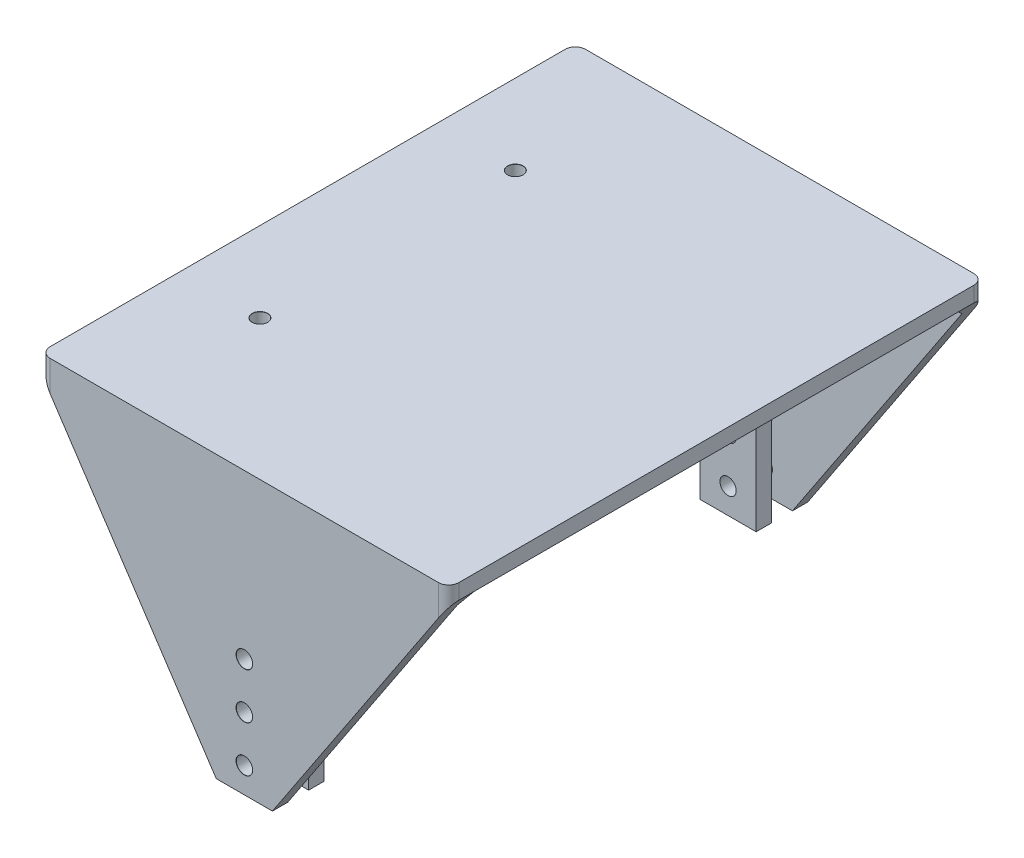
SolidWorks part; units mm, degrees
material "ABS"
ref_plane "Front Plane" through (0, 0, 0) normal (0, 0, 1) x (1, 0, 0)
ref_plane "Top Plane" through (0, 0, 0) normal (0, 1, 0) x (1, 0, 0)
ref_plane "Right Plane" through (0, 0, 0) normal (1, 0, 0) x (0, 0, -1)
sketch "Sketch1" plane through (0, 0, 0) normal (0, 1, 0) x (1, 0, 0)
  line L0 (-19.4927, 0) -> (33.7086, 0) construction
  line L1 (-40, -49.4) -> (40, -49.4)
  line L2 (-40, -49.4) -> (-40, 49.4)
  line L3 (-40, 49.4) -> (40, 49.4)
  line L4 (40, -49.4) -> (40, 49.4)
  line L5 (0, 23.6315) -> (0, -27.4954) construction
  point P0 (0, 0)
  point P10 (0, -27.4954)
  dimension "D1" = 80
  dimension "D2" = 98.8
extrude "Boss-Extrude1" add sketch "Sketch1" along normal blind 3
sketch "Sketch3" plane through (0, 0, 49.4) normal (0, 0, 1) x (1, 0, 0)
  line L0 (-40, 0) -> (-40, 3)
  line L1 (-40, 3) -> (40, 3)
  line L2 (40, 3) -> (40, 0) construction
  line L3 (-40, 3) -> (40, 3) construction
  line L4 (40, 3) -> (40, 0)
  line L5 (40, 0) -> (5.5, -52)
  line L6 (5.5, -52) -> (-5.5, -52)
  line L7 (-5.5, -52) -> (-40, 0)
  line L8 (0, 10.1365) -> (0, -10.768) construction
  dimension "D1" = 11
  dimension "D2" = 55
extrude "Boss-Extrude2" add sketch "Sketch3" along normal blind 3
mirror "Mirror1" about plane through (0, 0, 0) normal (0, 0, 1) of "Boss-Extrude2"
chamfer "Chamfer2" distance 2 angle 45 2 edges at (0, 0, -49.4) (0, 0, 49.4)
fillet "Fillet1" radius 2 4 edges at (-40, 1.5, 52.4) (-40, 1.5, -52.4) (40, 1.5, -52.4) (40, 1.5, 52.4)
sketch "Sketch4" plane through (0, 0, 49.4) normal (0, 0, -1) x (-1, 0, 0)
  line L0 (5.5, -52) -> (-5.5, -52) construction
  line L2 (-5.5, -19.9) -> (5.5, -19.9)
  line L3 (-5.5, -19.9) -> (-5.5, -22.9)
  line L4 (-5.5, -22.9) -> (5.5, -22.9)
  line L5 (5.5, -19.9) -> (5.5, -22.9)
  point P0 (0, 0)
  dimension "D1" = 29.1
  dimension "D2" = 3
extrude "Boss-Extrude3" add sketch "Sketch4" along normal blind 4.1
sketch "Sketch6" plane through (0, 0, 45.3) normal (0, 0, -1) x (-1, 0, 0)
  line L0 (5.5, -19.9) -> (-5.5, -19.9) construction
  line L1 (-5.5, -52) -> (5.5, -52)
  line L2 (-5.5, -52) -> (-5.5, -19.9)
  line L3 (-5.5, -19.9) -> (5.5, -19.9)
  line L4 (5.5, -52) -> (5.5, -19.9)
extrude "Boss-Extrude4" add sketch "Sketch6" along normal blind 3
mirror "Mirror4" about plane through (0, 0, 0) normal (0, 0, 1) of "Boss-Extrude4", "Boss-Extrude3"
chamfer "Chamfer3" distance 2 angle 45 2 edges at (0, -19.9, 49.4) (0, -19.9, -49.4)
hole_wizard "Ø3.0mm Dowel Hole1" positions "Sketch7" profile "Sketch8" hole size "Ø3.0" standard "ANSI Metric" end condition through all
sketch "Sketch7" plane through (0, 0, 52.4) normal (0, 0, 1) x (1, 0, 0)
  line L0 (-5.5, -52) -> (5.5, -52) construction
  point P0 (0, -47)
  point P2 (0, -38)
  point P4 (0, -29)
  dimension "D1" = 9
  dimension "D2" = 9
  dimension "D3" = 5
sketch "Sketch8" plane through (0, -47, 52.4) normal (1, 0, 0) x (0, -1, 0)
  line L0 (0, 0) -> (0, 104.8)
  line L1 (0, 104.8) -> (1.6, 104.8)
  line L2 (1.6, 104.8) -> (1.6, 0.025)
  line L3 (1.6, 0.025) -> (1.625, 0)
  line L5 (1.625, 0) -> (0, 0)
  line L6 (-1.6, 0.025) -> (-1.625, 0) construction
  line L11 (0, -6.35) -> (0, 107.95) construction
  dimension "Thru Hole Dia." = 3.2
  dimension "Thru Hole Depth" = 104.8
  dimension "Near C'Sink Dia." = 3.25
  dimension "Near C'Sink Angle" = 90
hole_wizard "Ø3.0mm Dowel Hole2" positions "Sketch9" profile "Sketch10" hole size "Ø3.0" standard "ANSI Metric"
sketch "Sketch9" plane through (0, 3, 0) normal (0, 1, 0) x (1, 0, 0)
  line L0 (-16.85, 25) -> (-31.85, 25) construction
  line L1 (-31.85, -25) -> (-16.85, -25) construction
  point P0 (-24.35, 25)
  point P4 (-24.35, -25)
sketch "Sketch10" plane through (-24.35, 3, -25) normal (1, 0, 0) x (0, 0, 1)
  line L0 (0, 0) -> (0, 20.9013)
  line L1 (0, 20.9013) -> (1.5, 20)
  line L2 (1.5, 20) -> (1.5, 0.025)
  line L3 (1.5, 0.025) -> (1.525, 0)
  line L5 (1.525, 0) -> (0, 0)
  line L6 (-1.5, 0.025) -> (-1.525, 0) construction
  line L10 (0, 20.9013) -> (-1.5, 20) construction
  line L11 (0, -6.35) -> (0, 107.95) construction
  dimension "Hole Dia." = 3
  dimension "Hole Depth" = 20
  dimension "Near C'Sink Dia." = 3.05
  dimension "Near C'Sink Angle" = 90
  dimension "Drill Angle" = 118
